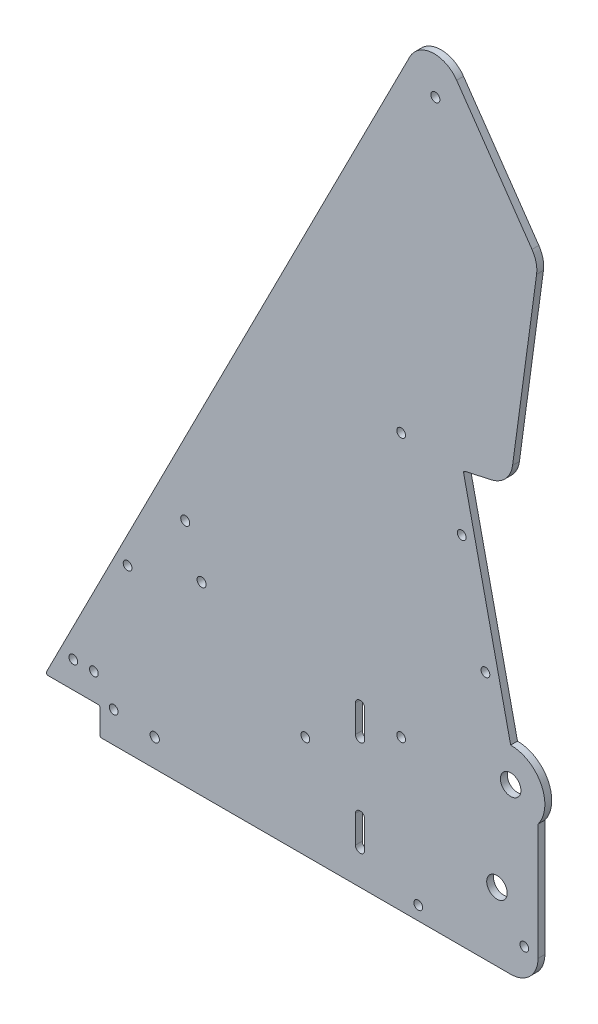
SolidWorks part; units mm, degrees
other "Markup1"
sketch "Sketch5"
ref_plane "Front Plane" through (0, 0, 0) normal (0, 0, 1) x (1, 0, 0)
ref_plane "Top Plane" through (0, 0, 0) normal (0, 1, 0) x (1, 0, 0)
ref_plane "Right Plane" through (0, 0, 0) normal (1, 0, 0) x (0, 0, -1)
sketch "Sketch1" plane through (0, 0, 0) normal (0, 0, 1) x (1, 0, 0)
  line L1 (228.6, -12.7) -> (228.6, 53.975)
  line L2 (178.7547, 351.4131) -> (0, 0)
  line L3 (228.6, 279.4) -> (178.7547, 351.4131)
  line L5 (0, 0) -> (25.4, 0)
  line L6 (25.4, 0) -> (25.4, -12.7)
  line L7 (25.4, -12.7) -> (228.6, -12.7)
  line L9 (215.9, 79.375) -> (193.9097, 178.5667)
  line L10 (193.9097, 178.5667) -> (215.6079, 183.377)
  line L11 (215.6079, 183.377) -> (228.6, 279.4)
  arc A0 (228.6, 53.975) -> (215.9, 79.375) centre (215.9, 63.5) ccw
  dimension "D7" = 12.7
  dimension "D8" = 76.2
  dimension "D10" = 31.75
  dimension "D2" = 292.1
  dimension "D3" = 25.4
  dimension "D4" = 215.9
  dimension "D5" = 394.2644
  dimension "D6" = 203.2
  dimension "D9" = 63.039
  dimension "D11" = 101.6
  dimension "D12" = 12.5
  dimension "D13" = 22.225
extrude "Boss-Extrude1" add sketch "Sketch1" along normal blind 3.175
sketch "Sketch2" plane through (0, 0, 3.175) normal (0, 0, 1) x (1, 0, 0)
  line L0 (178.7547, 351.4131) -> (0, 0) construction
  line L1 (25.4, -12.7) -> (228.6, -12.7) construction
  line L2 (215.9, 79.375) -> (193.9097, 178.5667) construction
  line L3 (193.9097, 178.5667) -> (215.6079, 183.377) construction
  line L4 (215.9, 79.375) -> (193.9097, 178.5667) construction
  line L5 (64.9432, 94.0578) -> (72.5445, 73.1732) construction
  line L6 (64.9432, 94.0578) -> (89.8317, 94.0578) construction
  line L10 (228.6, -12.7) -> (228.6, 53.975) construction
  circle A0 centre (64.9432, 94.0578) radius 2.0955
  circle A1 centre (180.975, 322.1643) radius 2.0955
  circle A2 centre (72.5445, 73.1732) radius 2.0955
  circle A3 centre (193.2078, 152.3944) radius 2.032
  circle A4 centre (215.9, 63.5) radius 4.7625
  circle A7 centre (173.0375, -6.35) radius 2.032
  circle A8 centre (204.203, 102.7985) radius 2.032
  circle A26 centre (209.55, 19.05) radius 4.7625
  arc A30 (228.6, 53.975) -> (215.9, 79.375) centre (215.9, 63.5) ccw construction
  circle A31 centre (165.1, 179.3875) radius 2.032
  dimension "D3" = 4.191
  dimension "D5" = 4.191
  dimension "D9" = 4.191
  dimension "D20" = 9.525
  dimension "D23" = 9.525
  dimension "D18" = 4.064
  dimension "D26" = 4.064
  dimension "D14" = 4.064
  dimension "D2" = 15.24
  dimension "D6" = 15.24
  dimension "D7" = 22.225
  dimension "D21" = 44.45
  dimension "D22" = 6.35
  dimension "D19" = 160.3375
  dimension "D24" = 44.45
  dimension "D25" = 6.35
  dimension "D27" = 25.4
  dimension "D28" = 50.8
  dimension "D29" = 6.35
  dimension "D17" = 6.35
  dimension "D33" = 55.5625
  dimension "D15" = 114.3
  dimension "D4" = 180.975
  dimension "D8" = 70
extrude "Cut-Extrude1" cut sketch "Sketch2" against normal through all
sketch "Sketch7" plane through (0, 0, 3.175) normal (0, 0, 1) x (1, 0, 0)
  line L0 (146.05, 3.175) -> (146.05, 15.875) construction
  line L1 (143.891, 3.175) -> (143.891, 15.875)
  line L2 (148.209, 3.175) -> (148.209, 15.875)
  line L3 (146.05, 47.625) -> (146.05, 60.325) construction
  line L4 (143.891, 47.625) -> (143.891, 60.325)
  line L5 (148.209, 47.625) -> (148.209, 60.325)
  line L6 (25.4, -12.7) -> (228.6, -12.7) construction
  line L12 (228.6, -12.7) -> (228.6, 53.975) construction
  line L13 (25.4, -12.7) -> (228.6, -12.7) construction
  arc A0 (143.891, 3.175) -> (148.209, 3.175) centre (146.05, 3.175) ccw
  arc A1 (148.209, 15.875) -> (143.891, 15.875) centre (146.05, 15.875) ccw
  arc A2 (143.891, 47.625) -> (148.209, 47.625) centre (146.05, 47.625) ccw
  arc A3 (148.209, 60.325) -> (143.891, 60.325) centre (146.05, 60.325) ccw
  circle A8 centre (50.8, 0) radius 2.159
  point P2 (146.05, 9.525)
  point P9 (146.05, 53.975)
  dimension "D1" = 4.318
  dimension "D5" = 4.318
  dimension "D2" = 12.7
  dimension "D3" = 12.7
  dimension "D4" = 44.45
  dimension "D6" = 95.25
  dimension "D7" = 82.55
  dimension "D8" = 15.875
  dimension "D9" = 12.7
extrude "Cut-Extrude2" cut sketch "Sketch7" against normal through all
sketch "Sketch10" plane through (0, 0, 3.175) normal (0, 0, 1) x (1, 0, 0)
  circle A1 centre (165.1, 57.15) radius 2.032
  circle A2 centre (120.65, 34.925) radius 2.032
  circle A3 centre (13.0465, 12.3347) radius 2.032
  circle A4 centre (22.5715, 12.3347) radius 2.032
  circle A5 centre (38.2114, 62.6398) radius 2.032
  dimension "D1" = 4.064
  dimension "D2" = 4.064
  dimension "D4" = 63.5
  dimension "D5" = 69.85
extrude "Cut-Extrude3" cut sketch "Sketch10" against normal up to next
fillet "Fillet1" radius 12.7 4 edges at (228.6, -12.7, 1.5875) (178.7547, 351.4131, 1.5875) (215.6079, 183.377, 1.5875) (228.6, 279.4, 1.5875)
fillet "Fillet2" radius 0.7937 4 edges at (25.4, -12.7, 1.5875) (25.4, 0, 1.5875) (193.9097, 178.5667, 1.5875) (0, 0, 1.5875)
sketch "Sketch12" plane through (0, 0, 3.175) normal (0, 0, 1) x (1, 0, 0)
  circle A0 centre (31.75, 1.5875) radius 2.032
  circle A1 centre (222.25, 1.5875) radius 2.032
  dimension "D1" = 4.064
extrude "Cut-Extrude5" cut sketch "Sketch12" against normal through all
equation "\"D6@Sketch2\"=\"D2@Sketch2\""
